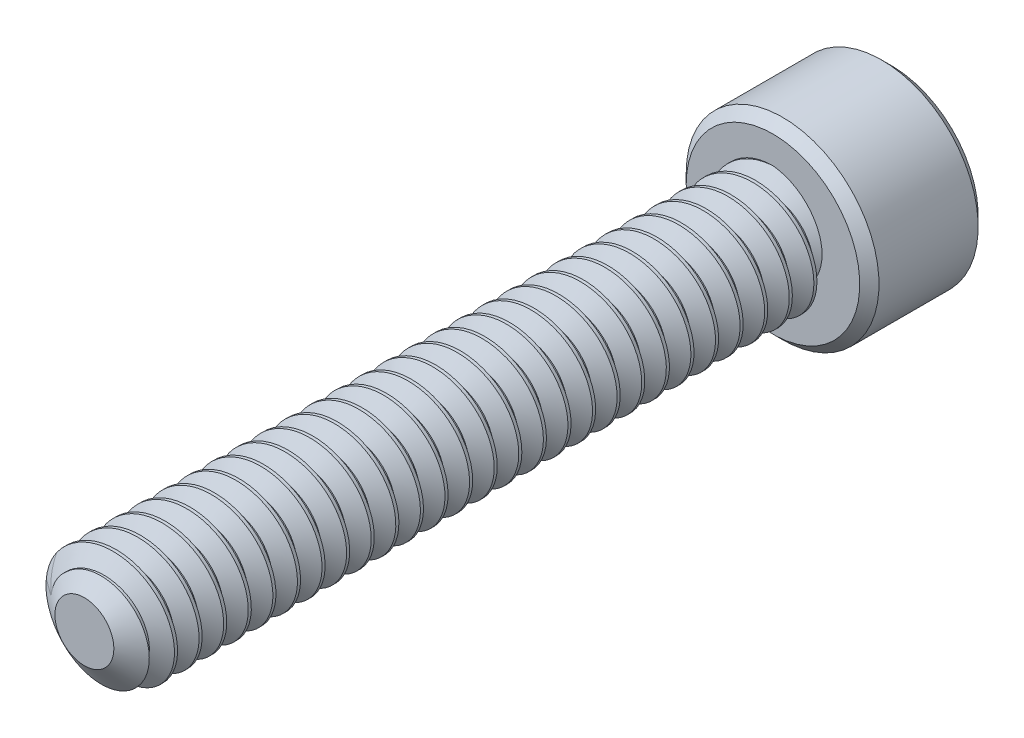
SolidWorks part; units mm, degrees
ref_plane "Front Plane" through (0, 0, 0) normal (0, 0, 1) x (1, 0, 0)
ref_plane "Top Plane" through (0, 0, 0) normal (0, 1, 0) x (1, 0, 0)
ref_plane "Right Plane" through (0, 0, 0) normal (1, 0, 0) x (0, 0, -1)
sketch "Sketch1" plane through (0, 0, 0) normal (0, 0, 1) x (1, 0, 0)
  circle A0 centre (0, 0) radius 1.0922
  dimension "OD" = 2.1844
extrude "Extrude1" add sketch "Sketch1" against normal blind 12.7
sketch "Sketch2" plane through (0, 0, 0) normal (0, 0, 1) x (1, 0, 0)
  circle A0 centre (0, 0) radius 1.0922 construction
  circle A1 centre (0, 0) radius 1.0922
curve "Helix/Spiral1" pitch 0.4536 height 13.1536 turns 29 parameters "pitch"=0.4536
sketch "Sketch3" plane through (0, 0, 0) normal (1, 0, 0) x (0, 0, -1)
  line L0 (-0.3969, 1.0922) -> (-0.2268, 0.7976)
  line L1 (-0.2268, 0.7976) -> (-0.1701, 0.7976)
  line L2 (-0.1701, 0.7976) -> (0, 1.0922)
  line L3 (-0.3969, 1.0922) -> (0, 1.0922)
  line L4 (-0.1984, 1.0922) -> (-0.1984, 0.7976) construction
  line L5 (-0.3118, 0.9449) -> (-0.085, 0.9449) construction
  line L6 (0, 1.0922) -> (0, -1.0922) construction
  dimension "D1" = 0.0567
  dimension "D2" = 0.2268
  dimension "D3" = 60
sweep "Cut-Sweep1" cut profiles "Sketch3" path "Helix/Spiral1"
sketch "Sketch4" plane through (0, 0, 0) normal (1, 0, 0) x (0, 0, -1)
  line L0 (0.3841, 1.0922) -> (0, 0.5436)
  line L1 (0, 0.5436) -> (0, 1.0922)
  line L2 (0.3841, 1.0922) -> (0, 1.0922)
  line L3 (-0.3969, 1.0922) -> (0, 1.0922) construction
  line L4 (0, 0) -> (7.0209, 0) construction
  dimension "D1" = 55
  dimension "D2" = 0.254
revolve "Cut-Revolve1" cut sketch "Sketch4" angle 360 about L4
sketch "Sketch5" plane through (0, 0, 0) normal (1, 0, 0) x (0, 0, -1)
  line L0 (12.7, -0.8061) -> (12.7, 0.7793) construction
  line L1 (12.7, 1.2192) -> (87.4665, 1.2192)
  line L2 (12.7, 1.2192) -> (12.7, 0)
  line L3 (12.7, 0) -> (87.3125, 0)
  line L4 (87.3125, 0.889) -> (87.3125, 0)
  line L5 (87.4665, 1.2192) -> (87.3125, 0.889)
  line L6 (0, 0) -> (9.9695, 0) construction
  point P3 (87.3125, 1.2192)
  point P10 (87.3125, 1.2192)
  dimension "D1" = 0.3302
  dimension "Thread min" = 87.3125
  dimension "D2" = 0.127
  dimension "D3" = 25
revolve "partially thread" [suppressed] add sketch "Sketch5" angle 360 about L6
sketch "Sketch6" plane through (0, 0, -12.7) normal (0, 0, -1) x (-1, 0, 0)
  circle A0 centre (0, 0) radius 1.778
  dimension "head dia" = 3.556
extrude "Extrude2" add sketch "Sketch6" along normal blind 2.1844
sketch "Sketch7" plane through (0, 0, -14.8844) normal (0, 0, -1) x (-1, 0, 0)
  line L1 (0, 1.1457) -> (-0.9922, 0.5728)
  line L2 (-0.9922, 0.5728) -> (-0.9922, -0.5728)
  line L3 (-0.9922, -0.5728) -> (0, -1.1457)
  line L4 (0, -1.1457) -> (0.9922, -0.5728)
  line L5 (0.9922, -0.5728) -> (0.9922, 0.5728)
  line L6 (0.9922, 0.5728) -> (0, 1.1457)
  circle A0 centre (0, 0) radius 0.9922 construction
  dimension "hex dia" = 1.9844
extrude "Cut-Extrude1" cut sketch "Sketch7" against normal blind 1.4883
sketch "Sketch8" plane through (0, 0, -14.8844) normal (0, 0, -1) x (-1, 0, 0)
  circle A0 centre (0, 0) radius 1.1457
extrude "Cut-Extrude2" cut sketch "Sketch8" against normal through all draft 45
chamfer "Chamfer1" distance 0.1778 angle 45 2 edges at (-1.778, 0, -14.8844) (-1.778, 0, -12.7)
sketch "Sketch9" plane through (0, 0, 0) normal (1, 0, 0) x (0, 0, -1)
  line L0 (0, 1.0922) -> (0, -1.0922) construction
  line L1 (2.4946, 1.0922) -> (2.4946, -1.0922) construction
  dimension "D1" = 2.4946
equation "\"D3@Helix/Spiral1\" = \"screw length@Extrude1\"+\"pitch@Helix/Spiral1\""
equation "\"D1@Sketch3\" = \"pitch@Helix/Spiral1\"*.125"
equation "\"D2@Sketch3\" = \"pitch@Helix/Spiral1\"*.5"
equation "\"D1@Cut-Extrude1\" = \"hex dia@Sketch7\"*.75"
equation "\"D1@Chamfer1\" = \"head dia@Sketch6\"*.05"
equation "\"D1@Sketch9\" = \"pitch@Helix/Spiral1\"*5.5"
